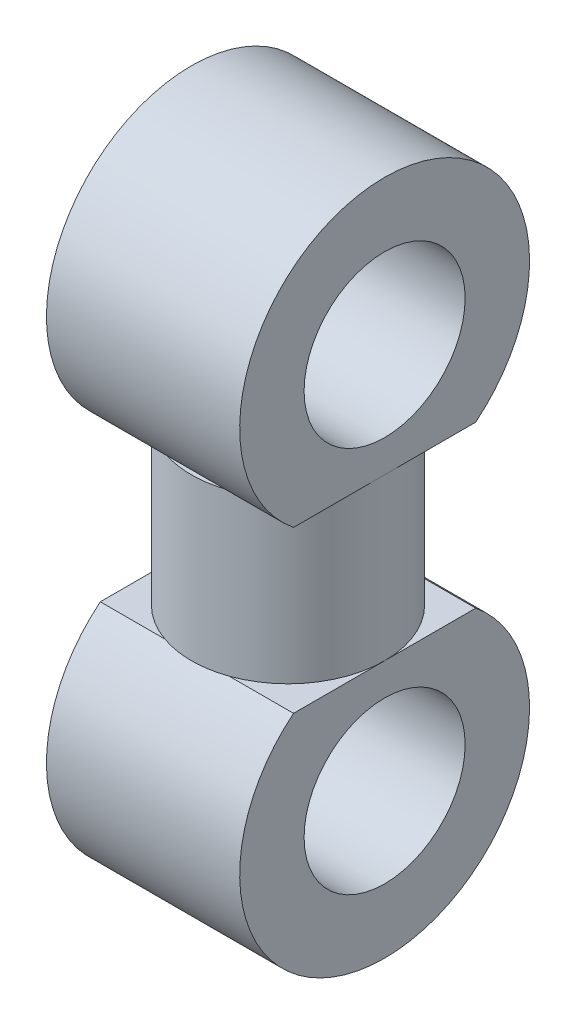
SolidWorks part; units mm, degrees
ref_plane "Front Plane" through (0, 0, 0) normal (0, 0, 1) x (1, 0, 0)
ref_plane "Top Plane" through (0, 0, 0) normal (0, 1, 0) x (1, 0, 0)
ref_plane "Right Plane" through (0, 0, 0) normal (1, 0, 0) x (0, 0, -1)
sketch "Sketch1" plane through (0, 0, 0) normal (0, 1, 0) x (1, 0, 0)
  circle A0 centre (0, 0) radius 3
  dimension "D1" = 6
extrude "crank_body" add sketch "Sketch1" along normal blind 4.5
sketch "Sketch2" plane through (0, 0, 0) normal (0, -1, 0) x (1, 0, 0)
  circle A0 centre (0, 0) radius 1.55
  dimension "D1" = 3.1
sketch "Sketch3" plane through (0, 0, 0) normal (1, 0, 0) x (0, 0, -1)
  line L0 (3, 4.5) -> (-3, 4.5) construction
  line L1 (-3, 4.5) -> (-3, 0) construction
  line L2 (-3, 4.5) -> (3, 4.5)
  line L3 (-3, 4.5) -> (-3, 5)
  line L4 (-3, 5) -> (3, 5)
  line L5 (3, 4.5) -> (3, 5)
  line L6 (3, 0) -> (3, 4.5) construction
  line L7 (-3, 4.5) -> (-3, 0) construction
  circle A0 centre (0, 8.5) radius 4.5
  dimension "D1" = 9
  dimension "D2" = 4
  dimension "D6" = 3
  dimension "D3" = 0.5
  dimension "D4" = 0
  dimension "D5" = 0
extrude "pin_shaft_body" add sketch "Sketch3" along normal blind 3 and the other way blind 3 contours A0 L3 L2 | L3 A0 L5 L4 | L5 A0 L3 L4 | L5 L4 L3 L2 region at (0, 4.6897, 2.6907) region at (0, 4.7628, 0) region at (0, 8.7525, 0)
sketch "Sketch4" plane through (3, 0, 0) normal (1, 0, 0) x (0, 0, -1)
  circle A0 centre (0, 8.5) radius 2.5
  dimension "D1" = 5
extrude "pin_shaft" cut sketch "Sketch4" against normal through all
extrude "smoothing_cuts" cut sketch "Sketch1<2>" along normal blind 5 flip side to cut
sketch "Sketch1<2>" plane through (0, 0, 0) normal (0, 1, 0) x (1, 0, 0) same geometry as "Sketch1"
ref_plane "Plane1" through (0, 2.5, 0) normal (0, -1, 0) x (-1, 0, 0)
mirror "Mirror1" about plane through (0, 2.5, 0) normal (0, -1, 0) of "smoothing_cuts", "pin_shaft_body", "pin_shaft"
